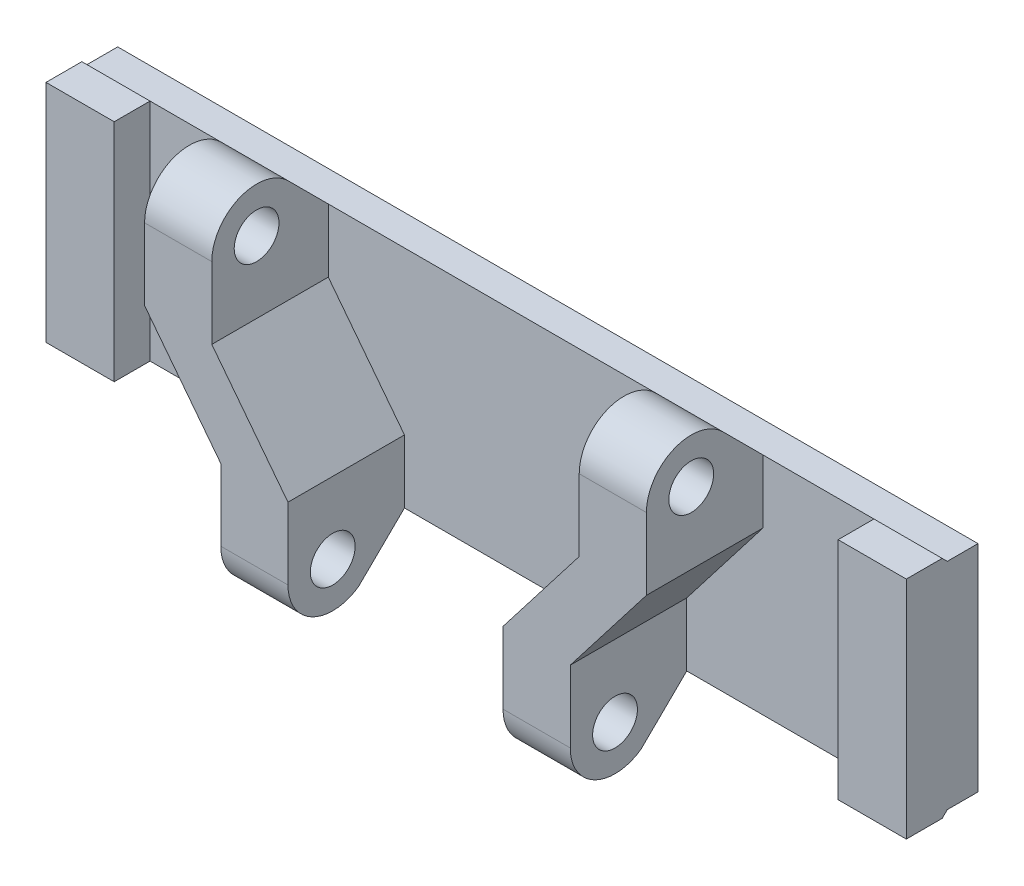
SolidWorks part; units mm, degrees
material "ABS"
ref_plane "Plano frontal" through (0, 0, 0) normal (0, 0, 1) x (1, 0, 0)
ref_plane "Plano superior" through (0, 0, 0) normal (0, 1, 0) x (1, 0, 0)
ref_plane "Plano direito" through (0, 0, 0) normal (1, 0, 0) x (0, 0, -1)
sketch "Esboço9" plane through (0, 0, 0) normal (1, 0, 0) x (0, 0, -1)
  line L0 (0, -6) -> (0, 6)
  line L1 (0, 6) -> (-1.7145, 6)
  line L2 (-1.7145, 6) -> (-4.2322, 8.5178)
  line L3 (-8.5, 6.75) -> (-8.5, -6.75)
  line L4 (-4.5643, -8.7948) -> (-1.7145, -6)
  line L5 (-1.7145, -6) -> (0, -6)
  line L6 (-8.5, 6.75) -> (-8.5, 7.6711) construction
  line L7 (-8.5, -6.75) -> (-8.5, -8.4052) construction
  arc A0 (-4.2322, 8.5178) -> (-8.5, 6.75) centre (-6, 6.75) ccw
  circle A1 centre (-6, 6.75) radius 1.25
  arc A2 (-8.5, -6.75) -> (-4.5643, -8.7948) centre (-6.0014, -6.7509) ccw
  circle A3 centre (-6.0014, -6.7509) radius 1.2506
extrude "Ressalto-extrusão2" add sketch "Esboço9" along normal mid plane 48
sketch "Esboço12" plane through (0, 0, 0) normal (0, 1, 0) x (1, 0, 0)
  line L0 (-24, -4) -> (-24, 0)
  line L1 (-24, 0) -> (24, 0)
  line L2 (24, 0) -> (24, -4)
  line L3 (24, -4) -> (20.1948, -4)
  line L4 (20.1948, -4) -> (20.1948, -2)
  line L5 (20.1948, -2) -> (14, -2)
  line L6 (14, -2) -> (14, -9.172)
  line L7 (14, -9.172) -> (6, -9.172)
  line L8 (6, -9.172) -> (6, -2)
  line L9 (6, -2) -> (-6, -2)
  line L10 (-6, -2) -> (-6, -9.172)
  line L11 (-6, -9.172) -> (-14, -9.172)
  line L12 (-14, -9.172) -> (-14, -2)
  line L13 (-14, -2) -> (-20.1948, -2)
  line L14 (-20.1948, -2) -> (-20.1948, -4)
  line L15 (-20.1948, -4) -> (-24, -4)
  line L16 (0, 0) -> (0, -6.686) construction
  line L18 (0, -2) -> (0, -1.7585) construction
  dimension "D1" = 12
  dimension "D2" = 8
extrude "Corte-extrusão5" cut sketch "Esboço12" against normal through all both and the other way through all flip side to cut
sketch "Esboço13" plane through (0, 0, 8.5) normal (0, 0, 1) x (1, 0, 0)
  line L0 (-14, 9.25) -> (-14, 2.75)
  line L2 (-14, 2.75) -> (-9.75, -2.7495)
  line L3 (-9.75, -2.7495) -> (-9.75, -9.2495)
  line L5 (-9.75, -9.2495) -> (-6, -9.2495)
  line L8 (-14, 9.25) -> (-10.25, 9.25)
  line L10 (-10.25, 9.25) -> (-10.25, 2.75)
  line L11 (-10.25, 2.75) -> (-6, -2.7495)
  line L13 (-6, -2.7495) -> (-6, -9.2495)
  line L14 (0, -213.271) -> (0, 62.4843) construction
  line L15 (6, -2.7495) -> (6, -9.2495)
  line L16 (10.25, 2.75) -> (6, -2.7495)
  line L17 (10.25, 9.25) -> (10.25, 2.75)
  line L18 (14, 9.25) -> (10.25, 9.25)
  line L19 (9.75, -9.2495) -> (6, -9.2495)
  line L20 (9.75, -2.7495) -> (9.75, -9.2495)
  line L21 (14, 2.75) -> (9.75, -2.7495)
  line L22 (14, 9.25) -> (14, 2.75)
  line L23 (-20.1948, 6.2855) -> (-24, 6.2855)
  line L24 (-18.3277, 13.1588) -> (17.8265, 13.1588)
  line L25 (-18.3277, 13.1588) -> (-18.3277, -18.0848)
  line L26 (-18.3277, -18.0848) -> (17.8265, -18.0848)
  line L27 (17.8265, 13.1588) -> (17.8265, -18.0848)
  line L28 (-24, -8.2414) -> (-24, 8.2855) construction
  line L29 (-24, 6.2855) -> (-24, 8.2855)
  line L30 (-24, 8.2855) -> (-20.1948, 8.2855)
  line L31 (-20.1948, 8.2855) -> (-20.1948, 6.2855)
  line L32 (-20.1948, -8.2414) -> (-20.1948, -6.28)
  line L33 (-20.1948, -6.28) -> (-24, -6.28)
  line L34 (-24, -6.28) -> (-24, -8.2414)
  line L35 (-24, -8.2414) -> (-20.1948, -8.2414)
  line L36 (24, 8.2855) -> (20.1948, 8.2855)
  line L37 (20.1948, 8.2855) -> (20.1948, 6.2855)
  line L38 (20.1948, 6.2855) -> (24, 6.2855)
  line L39 (24, -8.2414) -> (24, 8.2855) construction
  line L40 (24, 6.2855) -> (24, 8.2855)
  line L41 (20.1948, -6.28) -> (24, -6.28)
  line L42 (24, -6.28) -> (24, -8.2414)
  line L43 (24, -8.2414) -> (20.1948, -8.2414)
  line L44 (20.1948, -8.2414) -> (20.1948, -6.28)
extrude "Corte-extrusão6" cut sketch "Esboço13" against normal up to surface (6.5 mm away) and the other way blind 5000 up to face at (-17.0974, 0.0028, 2)
